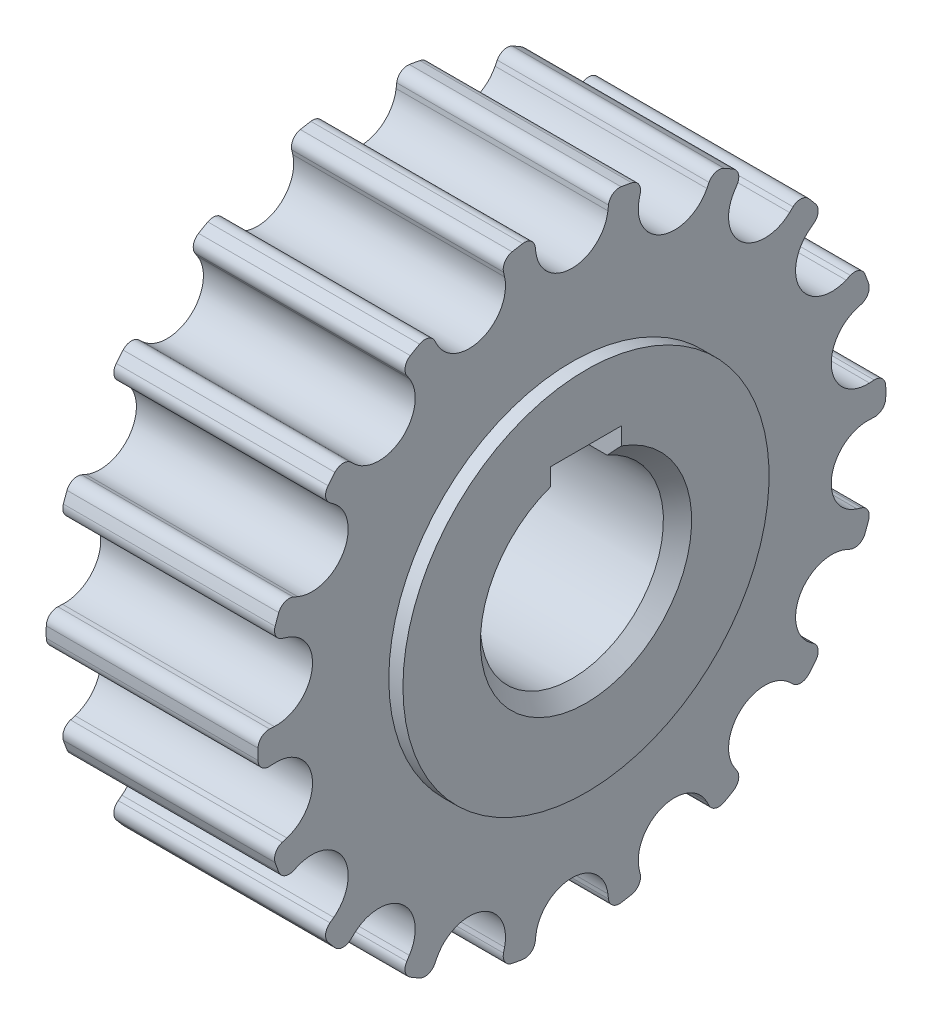
SolidWorks part; units mm, degrees
ref_plane "前视基准面" through (0, 0, 0) normal (0, 0, 1) x (1, 0, 0)
ref_plane "上视基准面" through (0, 0, 0) normal (0, 1, 0) x (1, 0, 0)
ref_plane "右视基准面" through (0, 0, 0) normal (1, 0, 0) x (0, 0, -1)
sketch "草图1" plane through (0, 0, 0) normal (0, 0, 1) x (1, 0, 0)
  line L0 (0, 0) -> (64.8368, 0) construction
  line L1 (0, 6.4838) -> (0, 22.234)
  line L2 (0, 22.234) -> (15, 22.234)
  line L3 (15, 22.234) -> (15, 12.9676)
  line L4 (15, 12.9676) -> (16, 12.9676)
  line L5 (16, 12.9676) -> (16, 6.4838)
  line L6 (16, 6.4838) -> (0, 6.4838)
  dimension "L" = 16
  dimension "B" = 15
  dimension "d" = 12.9676
  dimension "d1" = 25.9352
  dimension "da" = 44.468
revolve "旋转1" add sketch "草图1" angle 360 about L0
chamfer "倒角1" distance 1 angle 45 2 edges at (16, 0, 6.4838) (0, 0, 6.4838)
sketch "草图4" plane through (0, 0, 0) normal (-1, 0, 0) x (0, 0, 1)
  line L1 (-2.5, 5.9824) -> (2.5, 5.9824)
  line L2 (-2.5, 5.9824) -> (-2.5, 8.2824)
  line L3 (-2.5, 8.2824) -> (2.5, 8.2824)
  line L4 (2.5, 5.9824) -> (2.5, 8.2824)
  circle A0 centre (0, 0) radius 6.4838 construction
  dimension "键槽宽度" = 5
  dimension "t1" = 2.3
extrude "切除-拉伸1" cut sketch "草图4" against normal through all
ref_axis "基准轴1" through (-1.4, 0, 0) along (1, 0, 0)
sketch "草图6" plane through (0, 0, 0) normal (1, 0, 0) x (0, 0, -1)
  line L0 (0, 0) -> (0, 30.6512) construction
  line L1 (2.5917, 21.2834) -> (2.5508, 20.9508)
  line L2 (4.2563, 21.8228) -> (4.453, 23.4244)
  line L3 (-4.2563, 21.8228) -> (-4.453, 23.4244)
  line L4 (-2.5917, 21.2834) -> (-2.5508, 20.9508)
  circle A0 centre (0, 0) radius 22.234 construction
  circle A1 centre (0, 0) radius 18.694 construction
  arc A2 (-2.5508, 20.9508) -> (2.5508, 20.9508) centre (0, 21.264) ccw
  arc A3 (4.453, 23.4244) -> (-4.453, 23.4244) centre (0, 0) ccw
  arc A4 (2.5917, 21.2834) -> (3.4882, 21.9587) centre (3.3659, 21.1883) cw
  arc A5 (3.4882, 21.9587) -> (4.2563, 21.8228) centre (0, 0) cw
  arc A6 (-3.4882, 21.9587) -> (-4.2563, 21.8228) centre (0, 0) ccw
  arc A7 (-2.5917, 21.2834) -> (-3.4882, 21.9587) centre (-3.3659, 21.1883) ccw
  point P7 (0, 5.35)
  point P8 (0, 27.1112)
  point P15 (2.6884, 22.0709)
  dimension "D1" = 37.388
  dimension "ra" = 0.78
  dimension "rf" = 2.57
  dimension "hg" = 3.54
  dimension "D3" = 0.78
  dimension "D4" = 1.6136
  dimension "angle" = 14
  dimension "bw" = 5.35
extrude "切除-拉伸2" cut sketch "草图6" along normal up to next
pattern_circular "阵列(圆周)3" count 18 over 360 about axis through (-1.4, 0, 0) along (1, 0, 0) of "切除-拉伸2"
equation "\"D1@草图6\" = \"da@草图1\"  - \"hg@草图6\" - \"hg@草图6\""
equation "\"D3@草图6\" = \"ra@草图6\""
